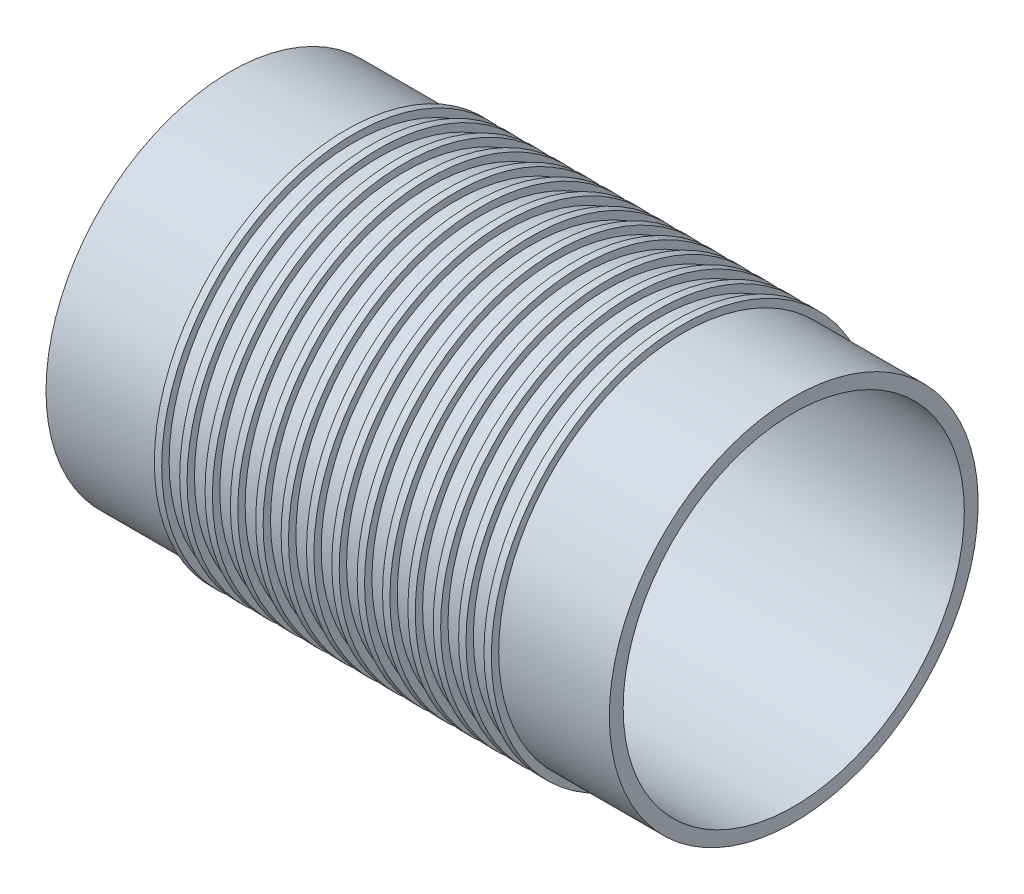
SolidWorks part; units mm, degrees
ref_plane "Front Plane" through (0, 0, 0) normal (0, 0, 1) x (1, 0, 0)
ref_plane "Top Plane" through (0, 0, 0) normal (0, 1, 0) x (1, 0, 0)
ref_plane "Right Plane" through (0, 0, 0) normal (1, 0, 0) x (0, 0, -1)
sketch "Sketch1" plane through (0, 0, 0) normal (0, 0, 1) x (1, 0, 0)
  line L0 (-100.1879, 0) -> (96.0625, 0) construction
  line L1 (55, 0) -> (-55, 0) construction
  line L2 (-30.55, 18.5) -> (30.55, 18.5)
  line L3 (0, 0) -> (0, 61.2914) construction
  line L4 (0, -55) -> (0, 55) construction
  line L5 (30.55, 18.5) -> (30.55, 20)
  line L6 (30.55, 20) -> (18.55, 20)
  line L7 (18.55, 20) -> (18.55, 20.8)
  line L8 (18.55, 20.8) -> (17.75, 20.8)
  line L9 (17.75, 20.8) -> (17.75, 20)
  line L10 (17.75, 20) -> (15.8, 20)
  line L11 (-30.55, 18.5) -> (-30.55, 20)
  line L12 (15, 20.8) -> (15, 20)
  line L13 (15.8, 20.8) -> (15, 20.8)
  line L14 (15.8, 20) -> (15.8, 20.8)
  line L15 (12.25, 20.8) -> (12.25, 20)
  line L16 (13.05, 20.8) -> (12.25, 20.8)
  line L17 (13.05, 20) -> (13.05, 20.8)
  line L18 (9.5, 20.8) -> (9.5, 20)
  line L19 (10.3, 20.8) -> (9.5, 20.8)
  line L20 (10.3, 20) -> (10.3, 20.8)
  line L21 (6.75, 20.8) -> (6.75, 20)
  line L22 (7.55, 20.8) -> (6.75, 20.8)
  line L23 (7.55, 20) -> (7.55, 20.8)
  line L24 (4, 20.8) -> (4, 20)
  line L25 (4.8, 20.8) -> (4, 20.8)
  line L26 (4.8, 20) -> (4.8, 20.8)
  line L27 (1.25, 20.8) -> (1.25, 20)
  line L28 (2.05, 20.8) -> (1.25, 20.8)
  line L29 (2.05, 20) -> (2.05, 20.8)
  line L30 (-1.5, 20.8) -> (-1.5, 20)
  line L31 (-0.7, 20.8) -> (-1.5, 20.8)
  line L32 (-0.7, 20) -> (-0.7, 20.8)
  line L33 (-4.25, 20.8) -> (-4.25, 20)
  line L34 (-3.45, 20.8) -> (-4.25, 20.8)
  line L35 (-3.45, 20) -> (-3.45, 20.8)
  line L36 (-7, 20.8) -> (-7, 20)
  line L37 (-6.2, 20.8) -> (-7, 20.8)
  line L38 (-6.2, 20) -> (-6.2, 20.8)
  line L39 (-9.75, 20.8) -> (-9.75, 20)
  line L40 (-8.95, 20.8) -> (-9.75, 20.8)
  line L41 (-8.95, 20) -> (-8.95, 20.8)
  line L42 (-12.5, 20.8) -> (-12.5, 20)
  line L43 (-11.7, 20.8) -> (-12.5, 20.8)
  line L44 (-11.7, 20) -> (-11.7, 20.8)
  line L45 (-15.25, 20.8) -> (-15.25, 20)
  line L46 (-14.45, 20.8) -> (-15.25, 20.8)
  line L47 (-14.45, 20) -> (-14.45, 20.8)
  line L48 (-18, 20.8) -> (-18, 20)
  line L49 (-17.2, 20.8) -> (-18, 20.8)
  line L50 (-17.2, 20) -> (-17.2, 20.8)
  line L78 (17.75, 20.8) -> (15, 20.8) construction
  line L79 (15, 20) -> (13.05, 20)
  line L80 (12.25, 20) -> (10.3, 20)
  line L81 (9.5, 20) -> (7.55, 20)
  line L82 (6.75, 20) -> (4.8, 20)
  line L83 (4, 20) -> (2.05, 20)
  line L84 (1.25, 20) -> (-0.7, 20)
  line L85 (-1.5, 20) -> (-3.45, 20)
  line L86 (-4.25, 20) -> (-6.2, 20)
  line L87 (-7, 20) -> (-8.95, 20)
  line L88 (-9.75, 20) -> (-11.7, 20)
  line L89 (-12.5, 20) -> (-14.45, 20)
  line L90 (-15.25, 20) -> (-17.2, 20)
  line L96 (-18, 20) -> (-30.55, 20)
  line L176 (-34.5, 20.8) -> (-34.5, 20) [skipped]
  line L177 (-33.7, 20.8) -> (-34.5, 20.8) [skipped]
  line L178 (-33.7, 20) -> (-33.7, 20.8) [skipped]
  line L179 (-37.25, 20.8) -> (-37.25, 20) [skipped]
  line L180 (-36.45, 20.8) -> (-37.25, 20.8) [skipped]
  line L181 (-36.45, 20) -> (-36.45, 20.8) [skipped]
  line L182 (-40, 20.8) -> (-40, 20) [skipped]
  line L183 (-39.2, 20.8) -> (-40, 20.8) [skipped]
  line L184 (-39.2, 20) -> (-39.2, 20.8) [skipped]
  line L185 (-42.75, 20.8) -> (-42.75, 20) [skipped]
  line L186 (-41.95, 20.8) -> (-42.75, 20.8) [skipped]
  line L187 (-41.95, 20) -> (-41.95, 20.8) [skipped]
  line L188 (-45.5, 20.8) -> (-45.5, 20) [skipped]
  line L189 (-44.7, 20.8) -> (-45.5, 20.8) [skipped]
  line L190 (-44.7, 20) -> (-44.7, 20.8) [skipped]
  line L191 (-48.25, 20.8) -> (-48.25, 20) [skipped]
  line L192 (-47.45, 20.8) -> (-48.25, 20.8) [skipped]
  line L193 (-47.45, 20) -> (-47.45, 20.8) [skipped]
  line L194 (-51, 20.8) -> (-51, 20) [skipped]
  line L195 (-50.2, 20.8) -> (-51, 20.8) [skipped]
  line L196 (-50.2, 20) -> (-50.2, 20.8) [skipped]
  line L197 (-20.75, 20.8) -> (-20.75, 20) [skipped]
  line L198 (-19.95, 20.8) -> (-20.75, 20.8) [skipped]
  line L199 (-19.95, 20) -> (-19.95, 20.8) [skipped]
  line L200 (-23.5, 20.8) -> (-23.5, 20) [skipped]
  line L201 (-22.7, 20.8) -> (-23.5, 20.8) [skipped]
  line L202 (-22.7, 20) -> (-22.7, 20.8) [skipped]
  line L203 (-26.25, 20.8) -> (-26.25, 20) [skipped]
  line L204 (-25.45, 20.8) -> (-26.25, 20.8) [skipped]
  line L205 (-25.45, 20) -> (-25.45, 20.8) [skipped]
  line L206 (-29, 20.8) -> (-29, 20) [skipped]
  line L207 (-28.2, 20.8) -> (-29, 20.8) [skipped]
  line L208 (-28.2, 20) -> (-28.2, 20.8) [skipped]
  line L209 (-31.75, 20.8) -> (-31.75, 20) [skipped]
  line L210 (-30.95, 20.8) -> (-31.75, 20.8) [skipped]
  line L211 (-30.95, 20) -> (-30.95, 20.8) [skipped]
  point P17 (-30.3489, 20)
  point P19 (-9.3087, 20)
  dimension "D1" = 40
  dimension "D2" = 1.5
  dimension "D3" = 41.6
  dimension "D4" = 0.8
  dimension "D5" = 12
  dimension "D6" = 61.1
  dimension "D8" = 2.75
  dimension "D7" = 26
revolve "Revolve1" add sketch "Sketch1" angle 360 about L0
